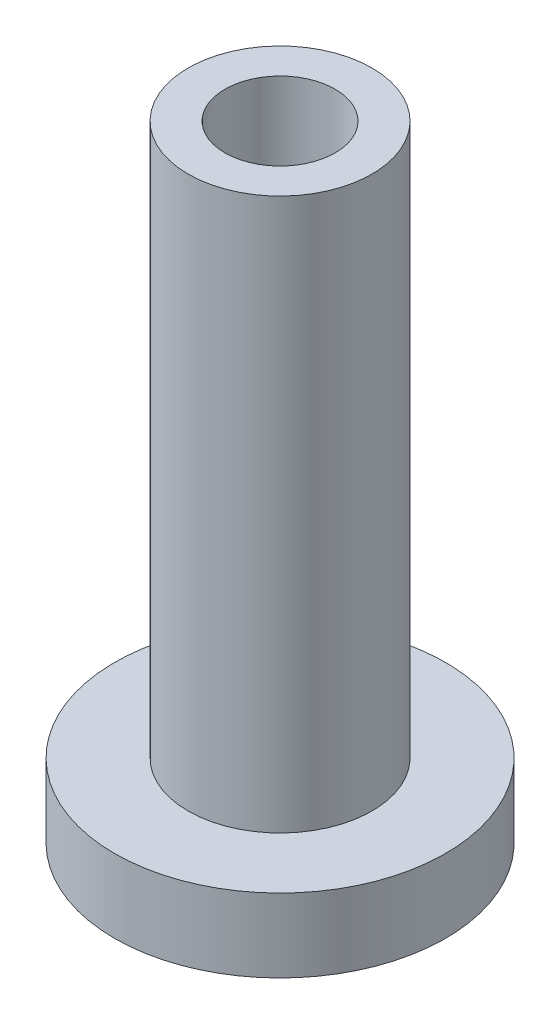
SolidWorks part; units mm, degrees
ref_plane "Front Plane" through (0, 0, 0) normal (0, 0, 1) x (1, 0, 0)
ref_plane "Top Plane" through (0, 0, 0) normal (0, 1, 0) x (1, 0, 0)
ref_plane "Right Plane" through (0, 0, 0) normal (1, 0, 0) x (0, 0, -1)
sketch "Sketch2" plane through (0, 0, 0) normal (0, 1, 0) x (1, 0, 0)
  circle A0 centre (0, 0) radius 2.5
  circle A1 centre (0, 0) radius 4.5
  dimension "D1" = 5
  dimension "D2" = 9
extrude "Boss-Extrude1" add sketch "Sketch2" against normal blind 2 contours A1 A0 | A0 region at (0, 0, 0) region at (-4.3727, 0, 0)
extrude "Boss-Extrude2" add sketch "Sketch2<3>" along normal blind 15 contours A0 region at (0, 0, 0)
sketch "Sketch2<3>" plane through (0, 0, 0) normal (0, 1, 0) x (1, 0, 0) same geometry as "Sketch2"
sketch "Sketch3" plane through (0, 15, 0) normal (0, 1, 0) x (1, 0, 0)
  circle A0 centre (0, 0) radius 1.5
  circle A1 centre (0, 0) radius 2.5 construction
  dimension "D1" = 1
extrude "Cut-Extrude1" cut sketch "Sketch3" along normal through all from surface starting at face at (0, 0, 2.5)
